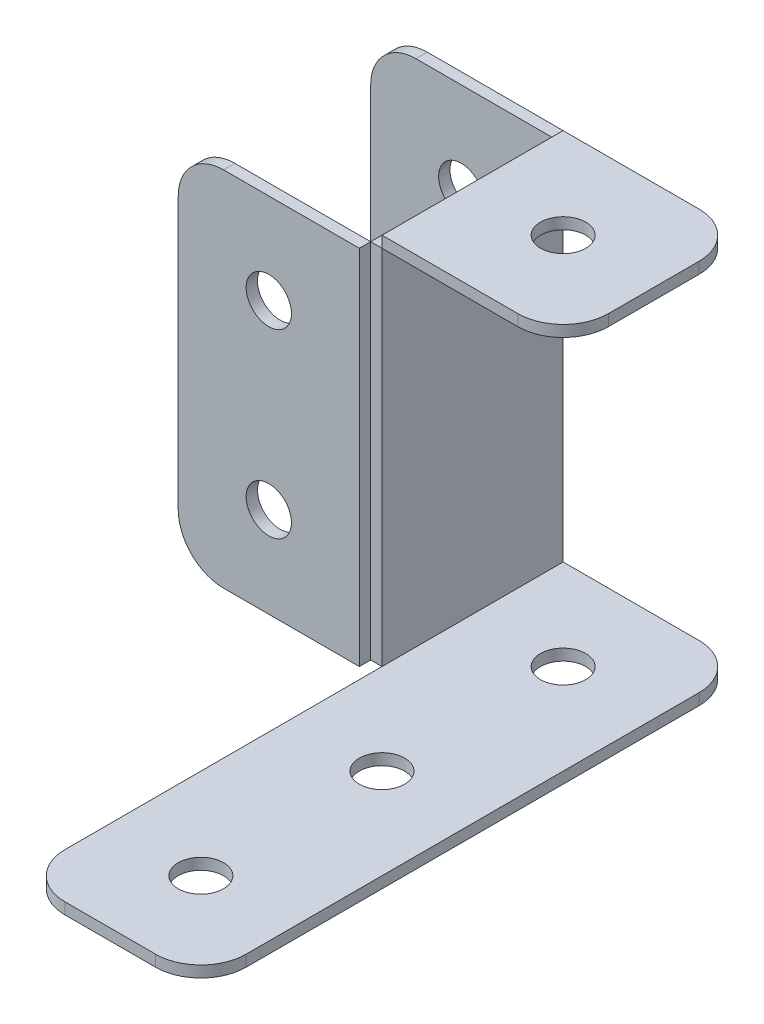
SolidWorks part; units mm, degrees
ref_plane "Front Plane" through (0, 0, 0) normal (0, 0, 1) x (1, 0, 0)
ref_plane "Top Plane" through (0, 0, 0) normal (0, 1, 0) x (1, 0, 0)
ref_plane "Right Plane" through (0, 0, 0) normal (1, 0, 0) x (0, 0, -1)
sketch "Sketch1" plane through (0, 0, 0) normal (0, 0, 1) x (1, 0, 0)
  line L0 (0, 0) -> (-25.4, 0)
  line L1 (-25.4, 0) -> (-25.4, 50.8)
  line L2 (-25.4, 50.8) -> (0, 50.8)
  line L3 (0, 50.8) -> (0, 0)
  line L4 (-12.7, 50.8) -> (-12.7, 0) construction
  circle A0 centre (-12.7, 38.1) radius 3.175
  circle A1 centre (-12.7, 12.7) radius 3.175
  dimension "D5" = 6.35
  dimension "D1" = 12.7
  dimension "D2" = 25.4
  dimension "D3" = 12.7
  dimension "D4" = 25.4
extrude "Boss-Extrude1" add sketch "Sketch1" along normal blind 1.5875
extrude "Boss-Extrude2" add sketch "Sketch1<2>" against normal blind 1.5875 from offset 25.4 separate body offset against normal yes
sketch "Sketch1<2>" plane through (0, 0, 0) normal (0, 0, 1) x (1, 0, 0) same geometry as "Sketch1"
sketch "Sketch3" plane through (0, 0, 0) normal (1, 0, 0) x (0, 0, -1)
  line L1 (25.4, 50.8) -> (0, 50.8)
  line L2 (25.4, 50.8) -> (25.4, 0)
  line L3 (25.4, 0) -> (0, 0)
  line L4 (0, 50.8) -> (0, 0)
extrude "Boss-Extrude3" add sketch "Sketch3" along normal blind 1.5875 separate body
sketch "Sketch4" plane through (0, 0, 0) normal (0, 1, 0) x (1, 0, 0)
  line L1 (1.5875, -50.8) -> (26.9875, -50.8)
  line L3 (26.9875, 50.8) -> (1.5875, 50.8) construction
  line L4 (1.5875, 50.8) -> (1.5875, 25.4) construction
  line L5 (1.5875, 25.4) -> (1.5875, 0)
  line L6 (1.5875, 25.4) -> (26.9875, 25.4)
  line L7 (26.9875, 50.8) -> (26.9875, 25.4) construction
  line L8 (1.5875, -25.4) -> (26.9875, -25.4) construction
  line L9 (14.2875, -50.8) -> (14.2875, 50.8) construction
  line L10 (26.9875, -25.4) -> (26.9875, -50.8)
  line L11 (1.5875, 0) -> (1.5875, -25.4)
  line L12 (1.5875, -50.8) -> (1.5875, -25.4)
  line L13 (26.9875, -25.4) -> (26.9875, 25.4)
  circle A0 centre (14.2875, 12.7) radius 3.175
  circle A1 centre (14.2875, -12.7) radius 3.175
  circle A2 centre (14.2875, -38.1) radius 3.175
  circle A3 centre (14.2875, 38.1) radius 3.175 construction
  point P21 (17.9824, 38.1)
  dimension "D2" = 6.35
  dimension "D1" = 12.7
  dimension "D3" = 12.7
  dimension "D4" = 25.4
  dimension "D5" = 12.7
  dimension "D6" = 12.7
  dimension "D7" = 12.7
  dimension "D8" = 12.7
  dimension "D9" = 25.4
extrude "Boss-Extrude4" add sketch "Sketch4" against normal blind 1.5875 separate body
sketch "Sketch5" plane through (0, 50.8, 0) normal (0, 1, 0) x (1, 0, 0)
  line L1 (1.5875, 25.4) -> (26.9875, 25.4)
  line L2 (1.5875, 25.4) -> (1.5875, 0)
  line L3 (1.5875, 0) -> (26.9875, 0)
  line L4 (26.9875, 25.4) -> (26.9875, 0)
  circle A0 centre (14.2875, 12.7) radius 3.175
  dimension "D4" = 6.35
  dimension "D1" = 25.4
  dimension "D2" = 12.7
  dimension "D3" = 12.7
extrude "Boss-Extrude5" add sketch "Sketch5" along normal blind 1.5875 separate body
fillet "Fillet1" radius 6.35 3 edges at (26.9875, -0.7937, -25.4) (26.9875, -0.7937, 50.8) (1.5875, -0.7937, 50.8)
fillet "Fillet2" radius 6.35 2 edges at (-25.4, 0, -26.1937) (-25.4, 50.8, -26.1937)
fillet "Fillet3" radius 6.35 2 edges at (-25.4, 50.8, 0.7937) (-25.4, 0, 0.7937)
fillet "Fillet4" radius 6.35 2 edges at (26.9875, 51.5938, -25.4) (26.9875, 51.5938, 0)
